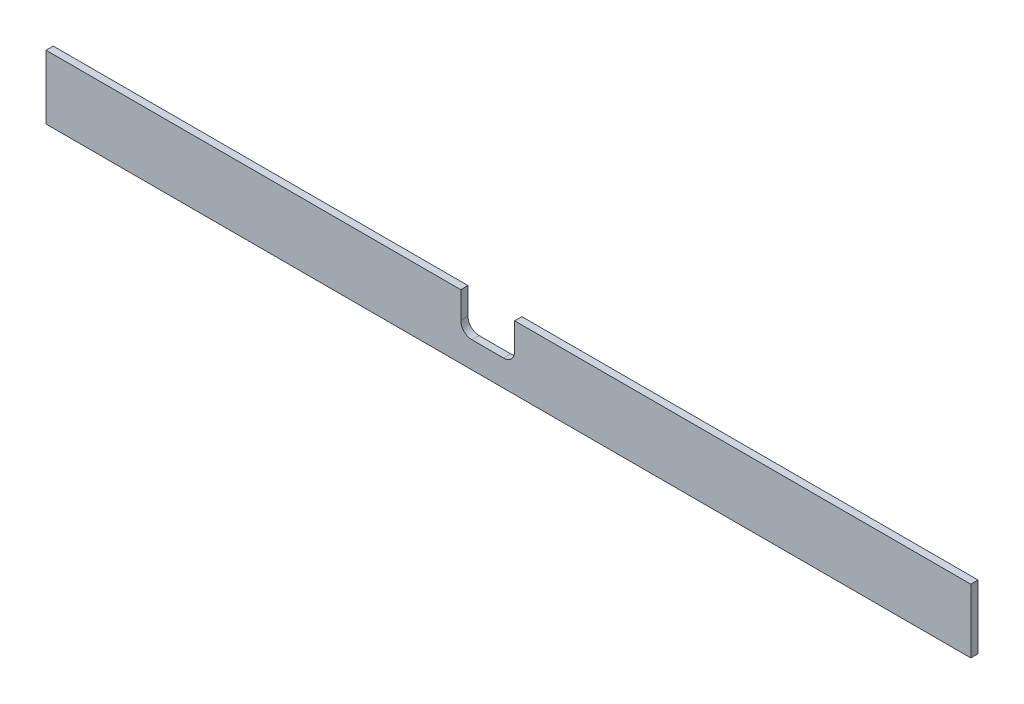
SolidWorks part; units mm, degrees
ref_plane "Plan de face" through (0, 0, 0) normal (0, 0, 1) x (1, 0, 0)
ref_plane "Plan de dessus" through (0, 0, 0) normal (0, 1, 0) x (1, 0, 0)
ref_plane "Plan de droite" through (0, 0, 0) normal (1, 0, 0) x (0, 0, -1)
sketch "Esquisse1" plane through (0, 0, 0) normal (0, 0, 1) x (1, 0, 0)
  line L1 (-416, -28.75) -> (416, -28.75)
  line L2 (-416, -28.75) -> (-416, 28.75)
  line L3 (-416, 28.75) -> (416, 28.75)
  line L4 (416, -28.75) -> (416, 28.75)
  line L5 (-416, -28.75) -> (416, 28.75) construction
  line L6 (-416, 28.75) -> (416, -28.75) construction
  point P0 (0, 0)
  dimension "D1" = 57.5
  dimension "D2" = 832
extrude "Boss.-Extru.1" add sketch "Esquisse1" along normal blind 6.5
sketch "Esquisse2" plane through (0, 0, 0) normal (0, 0, -1) x (-1, 0, 0)
  line L0 (416, -28.75) -> (-416, -28.75) construction
  line L1 (4.37, -5.25) -> (32.844, -5.25)
  line L2 (-5.63, 4.75) -> (-5.63, 32.7961)
  line L3 (4.37, 42.7961) -> (32.844, 42.7961)
  line L4 (42.844, 4.75) -> (42.844, 32.7961)
  line L5 (-5.63, -5.25) -> (42.844, 42.7961) construction
  line L6 (-5.63, 42.7961) -> (42.844, -5.25) construction
  line L7 (-416, -28.75) -> (-416, 28.75) construction
  arc A0 (42.844, 4.75) -> (32.844, -5.25) centre (32.844, 4.75) cw
  arc A1 (4.37, -5.25) -> (-5.63, 4.75) centre (4.37, 4.75) cw
  arc A2 (-5.63, 32.7961) -> (4.37, 42.7961) centre (4.37, 32.7961) cw
  arc A3 (42.844, 32.7961) -> (32.844, 42.7961) centre (32.844, 32.7961) ccw
  point P0 (18.607, 18.7731)
  dimension "D1" = 10
  dimension "D2" = 23.5
  dimension "D3" = 410.37
  dimension "D4" = 28.0461
  dimension "D5" = 48.474
extrude "Enlèv. mat.-Extru.1" cut sketch "Esquisse2" against normal through all
ref_axis "Axe1" through (390.0984, 28.75, 0) along (-0.9893, -0.1458, 0)
